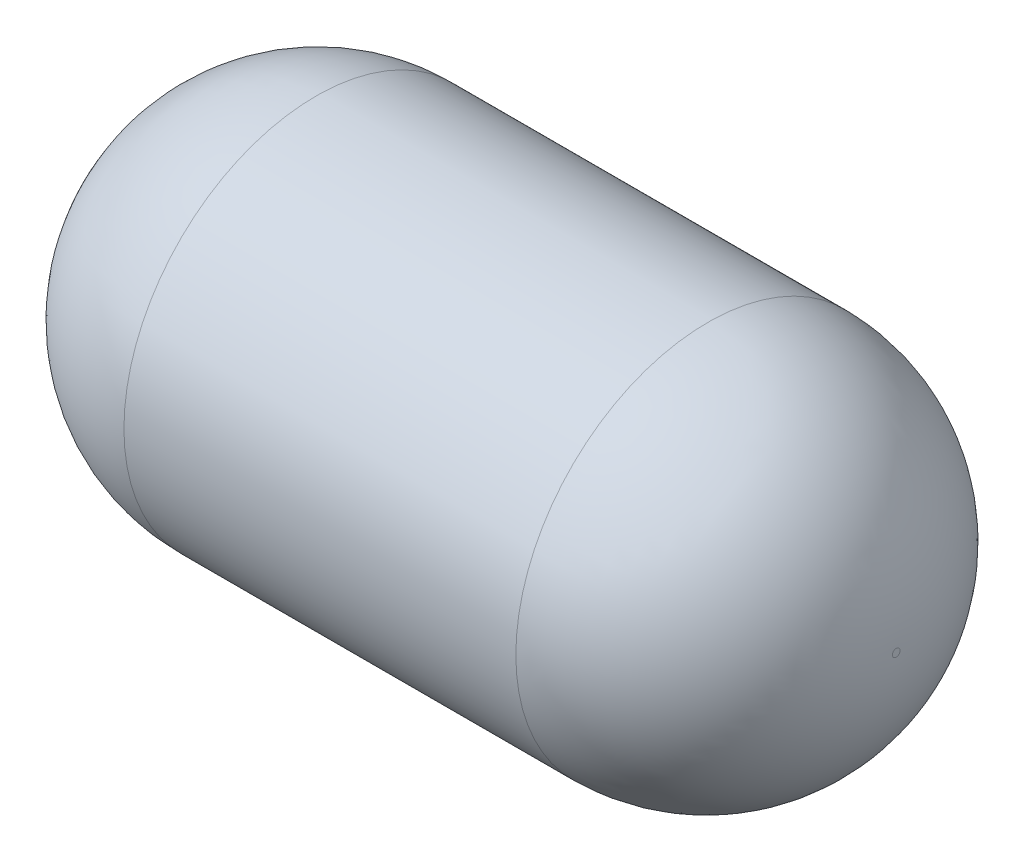
SolidWorks part; units mm, degrees
ref_plane "Front Plane" through (0, 0, 0) normal (0, 0, 1) x (1, 0, 0)
ref_plane "Top Plane" through (0, 0, 0) normal (0, 1, 0) x (1, 0, 0)
ref_plane "Right Plane" through (0, 0, 0) normal (1, 0, 0) x (0, 0, -1)
sketch "Sketch1" plane through (0, 0, 0) normal (0, 1, 0) x (1, 0, 0)
  line L1 (0, 0) -> (20, 0)
  line L2 (0, 0) -> (0, 0.1)
  line L3 (4.9, 5) -> (15.1, 5)
  line L4 (20, 0) -> (20, 0.1)
  arc A0 (15.1, 5) -> (20, 0.1) centre (15.1, 0.1) cw
  arc A1 (0, 0.1) -> (4.9, 5) centre (4.9, 0.1) cw
  point P6 (20, 5)
  point P10 (0, 5)
  dimension "D3" = 4.9
  dimension "D1" = 20
  dimension "D2" = 5
revolve "Revolve2" add sketch "Sketch1" angle 360 about L1
ref_plane "Plane1" through (5, 0, 0) normal (1, 0, 0) x (0, 0, -1)
sketch "Sketch3" plane through (5, 0, 0) normal (1, 0, 0) x (0, 0, -1)
  circle A0 centre (0.1, 0) radius 3.7633
  circle A1 centre (0, 0) radius 0.1 construction
extrude "Boss-Extrude2" add sketch "Sketch3" along normal blind 1 separate body
ref_plane "Plane2" through (0, 0, 3) normal (0, 0, 1) x (1, 0, 0)
sketch "Sketch4" plane through (0, 0, 3) normal (0, 0, 1) x (1, 0, 0)
  line L1 (6.137, 2.9988) -> (15.1178, 2.9988)
  line L2 (6.137, 2.9988) -> (6.137, -3.2946)
  line L3 (6.137, -3.2946) -> (15.1178, -3.2946)
  line L4 (15.1178, 2.9988) -> (15.1178, -3.2946)
  line L5 (6.137, 2.9988) -> (15.1178, -3.2946) construction
  line L6 (6.137, -3.2946) -> (15.1178, 2.9988) construction
  point P0 (10.6274, -0.1479)
  point P5 (10.6274, -0.1479)
extrude "Boss-Extrude3" add sketch "Sketch4" against normal blind 1 separate body
ref_plane "Plane3" through (0, 3, 0) normal (0, 1, 0) x (1, 0, 0)
sketch "Sketch5" plane through (0, 3, 0) normal (0, 1, 0) x (1, 0, 0)
  line L1 (4.7651, 2.9395) -> (15.3944, 2.9395)
  line L2 (4.7651, 2.9395) -> (4.7651, -2.9395)
  line L3 (4.7651, -2.9395) -> (15.3944, -2.9395)
  line L4 (15.3944, 2.9395) -> (15.3944, -2.9395)
  line L5 (4.7651, 2.9395) -> (15.3944, -2.9395) construction
  line L6 (4.7651, -2.9395) -> (15.3944, 2.9395) construction
  point P0 (10.0798, 0)
  point P5 (10.0798, 0)
extrude "Boss-Extrude4" add sketch "Sketch5" along normal blind 1 separate body
sketch "Sketch6" plane through (0, 4, 0) normal (0, 1, 0) x (1, 0, 0)
  line L0 (4.9966, 2.6923) -> (4.9966, -2.7827)
  line L1 (4.9966, -2.7827) -> (15.2621, -2.7827)
  line L2 (15.2621, -2.7827) -> (15.2621, 2.6923)
  line L3 (15.2621, 2.6923) -> (4.9966, 2.6923)
  line L4 (5.0966, 2.5923) -> (5.0966, -2.6827)
  line L5 (5.0966, -2.6827) -> (15.1621, -2.6827)
  line L6 (15.1621, -2.6827) -> (15.1621, 2.5923)
  line L7 (15.1621, 2.5923) -> (5.0966, 2.5923)
  line L8 (5.1966, 2.4923) -> (5.1966, -2.5827)
  line L9 (5.1966, -2.5827) -> (15.0621, -2.5827)
  line L10 (15.0621, -2.5827) -> (15.0621, 2.4923)
  line L11 (15.0621, 2.4923) -> (5.1966, 2.4923)
  line L12 (5.2966, 2.3923) -> (5.2966, -2.4827)
  line L13 (5.2966, -2.4827) -> (14.9621, -2.4827)
  line L14 (14.9621, -2.4827) -> (14.9621, 2.3923)
  line L15 (14.9621, 2.3923) -> (5.2966, 2.3923)
  line L16 (5.3966, 2.2923) -> (5.3966, -2.3827)
  line L17 (5.3966, -2.3827) -> (14.8621, -2.3827)
  line L18 (14.8621, -2.3827) -> (14.8621, 2.2923)
  line L19 (14.8621, 2.2923) -> (5.3966, 2.2923)
  line L20 (5.4966, 2.1923) -> (5.4966, -2.2827)
  line L21 (5.4966, -2.2827) -> (14.7621, -2.2827)
  line L22 (14.7621, -2.2827) -> (14.7621, 2.1923)
  line L23 (14.7621, 2.1923) -> (5.4966, 2.1923)
  line L24 (5.5966, 2.0923) -> (5.5966, -2.1827)
  line L25 (5.5966, -2.1827) -> (14.6621, -2.1827)
  line L26 (14.6621, -2.1827) -> (14.6621, 2.0923)
  line L27 (14.6621, 2.0923) -> (5.5966, 2.0923)
  line L28 (5.6966, 1.9923) -> (5.6966, -2.0827)
  line L29 (5.6966, -2.0827) -> (14.5621, -2.0827)
  line L30 (14.5621, -2.0827) -> (14.5621, 1.9923)
  line L31 (14.5621, 1.9923) -> (5.6966, 1.9923)
  dimension "D1" = 0.1
  dimension "D2" = 0.2
  dimension "D3" = 0.4
sketch "Sketch8" plane through (0, 0, 2) normal (0, 0, -1) x (-1, 0, 0)
  line L0 (-14.7193, 2.6932) -> (-6.4312, 2.6932)
  line L1 (-14.9193, 2.8932) -> (-6.2312, 2.8932)
  line L2 (-14.9193, 2.8932) -> (-14.9193, -3.2071)
  line L3 (-14.9193, -3.2071) -> (-6.2312, -3.2071)
  line L4 (-6.2312, 2.8932) -> (-6.2312, -3.2071)
  line L5 (-14.8092, 2.7611) -> (-6.3634, 2.7611)
  line L6 (-14.8092, 2.7611) -> (-14.8092, -3.075)
  line L7 (-14.8092, -3.075) -> (-6.3634, -3.075)
  line L8 (-6.3634, 2.7611) -> (-6.3634, -3.075)
  line L9 (-6.4312, 2.6932) -> (-6.4312, -3.0071)
  line L10 (-14.7193, -3.0071) -> (-6.4312, -3.0071)
  line L11 (-14.7193, 2.6932) -> (-14.7193, -3.0071)
  line L12 (-14.6092, 2.5611) -> (-6.5634, 2.5611)
  line L13 (-6.5634, 2.5611) -> (-6.5634, -2.875)
  line L14 (-14.6092, -2.875) -> (-6.5634, -2.875)
  line L15 (-14.6092, 2.5611) -> (-14.6092, -2.875)
  line L16 (-14.3193, 2.2932) -> (-6.8312, 2.2932)
  line L17 (-6.8312, 2.2932) -> (-6.8312, -2.6071)
  line L18 (-14.3193, -2.6071) -> (-6.8312, -2.6071)
  line L19 (-14.3193, 2.2932) -> (-14.3193, -2.6071)
  line L20 (-14.5193, 2.4932) -> (-6.6312, 2.4932)
  line L21 (-6.6312, 2.4932) -> (-6.6312, -2.8071)
  line L22 (-14.5193, -2.8071) -> (-6.6312, -2.8071)
  line L23 (-14.5193, 2.4932) -> (-14.5193, -2.8071)
  line L24 (-14.4092, 2.3611) -> (-6.7634, 2.3611)
  line L25 (-6.7634, 2.3611) -> (-6.7634, -2.675)
  line L26 (-14.4092, -2.675) -> (-6.7634, -2.675)
  line L27 (-14.4092, 2.3611) -> (-14.4092, -2.675)
  line L28 (-14.2092, 2.1611) -> (-6.9634, 2.1611)
  line L29 (-6.9634, 2.1611) -> (-6.9634, -2.475)
  line L30 (-14.2092, -2.475) -> (-6.9634, -2.475)
  line L31 (-14.2092, 2.1611) -> (-14.2092, -2.475)
  dimension "D1" = 0.2
  dimension "D2" = 0.4
extrude "Boss-Extrude5" add sketch "Sketch6" along normal blind 0.01 contours L2 L3 L0 L1 L7 L6 L5 L4 | L10 L11 L8 L9 L15 L14 L13 L12 | L18 L19 L16 L17 L23 L22 L21 L20 | L26 L27 L24 L25 L31 L30 L29 L28 region at (10.1294, 4, -2.6806) region at (10.1294, 4, -2.4812) region at (10.1294, 4, -2.2817) region at (10.1294, 4, -2.0822)
extrude "Boss-Extrude6" add sketch "Sketch8" along normal blind 0.01 contours L4 L1 L2 L3 L5 L8 L7 L6 | L0 L11 L10 L9 L15 L12 L13 L14 | L24 L27 L26 L25 L19 L16 L17 L18 region at (10.5753, 2.5926, 2) region at (10.5753, 2.7871, 2) region at (10.5863, 2.3519, 2)
sketch "Sketch9" plane through (6, 0, 0) normal (1, 0, 0) x (0, 0, -1)
  circle A0 centre (0, 0) radius 3.6202
  circle A1 centre (0, 0) radius 3.5411
  circle A2 centre (0, 0) radius 3.4702
  circle A3 centre (0, 0) radius 3.3911
  circle A4 centre (0, 0) radius 3.3202
  circle A5 centre (0, 0) radius 3.2411
  circle A6 centre (0, 0) radius 3.1702
  circle A7 centre (0, 0) radius 3.0911
  dimension "D1" = 0.15
  dimension "D2" = 0.3
extrude "Boss-Extrude7" add sketch "Sketch9" along normal blind 0.01 contours A0 A1 | A2 A3 | A4 A5 | A6 A7 region at (6, 0, 3.6099) region at (6, 0, 3.4604) region at (6, 0, 3.3108) region at (6, 0, 3.1612)
ref_plane "Plane4" through (8, 0, 0) normal (1, 0, 0) x (0, 0, -1)
sketch "Sketch10" plane through (8, 0, 0) normal (1, 0, 0) x (0, 0, -1)
  line L1 (-1.6182, 2.7298) -> (3.0085, 2.7298)
  line L2 (-1.6182, 2.7298) -> (-1.6182, -3.0108)
  line L3 (-1.6182, -3.0108) -> (3.0085, -3.0108)
  line L4 (3.0085, 2.7298) -> (3.0085, -3.0108)
  line L5 (-1.788, 2.8149) -> (3.157, 2.8149)
  line L6 (-1.788, 2.8149) -> (-1.788, -3.2195)
  line L7 (-1.788, -3.2195) -> (3.157, -3.2195)
  line L8 (3.157, 2.8149) -> (3.157, -3.2195)
extrude "Boss-Extrude8" add sketch "Sketch10" along normal blind 1 separate body contours L8 L5 L6 L7 L1 L4 L3 L2 | L4 L1 L2 L3 region at (8, -0.1405, -0.6951) region at (8, 2.7369, -0.6845)
extrude "Boss-Extrude9" add sketch "Sketch10<3>" along normal blind 2 from offset 1.5 separate body contours L4 L1 L2 L3 region at (8, -0.1405, -0.6951)
sketch "Sketch10<3>" plane through (8, 0, 0) normal (1, 0, 0) x (0, 0, -1) same geometry as "Sketch10"
ref_plane "Plane5" through (14, 0, 0) normal (1, 0, 0) x (0, 0, -1)
sketch "Sketch11" plane through (14, 0, 0) normal (1, 0, 0) x (0, 0, -1)
  circle A0 centre (0.1, 0) radius 1.9739
  circle A1 centre (0, 0) radius 0.1 construction
extrude "Boss-Extrude10" add sketch "Sketch11" along normal mid plane 4 separate body
sketch "Sketch12" plane through (16, 0, 0) normal (1, 0, 0) x (0, 0, -1)
  line L0 (0.1, 1.7403) -> (0.1, -1.7403)
  arc A0 (0.1, -1.7403) -> (0.1, 1.7403) centre (0.1, 0) ccw
revolve "Revolve3" add sketch "Sketch12" angle 360 about L0
